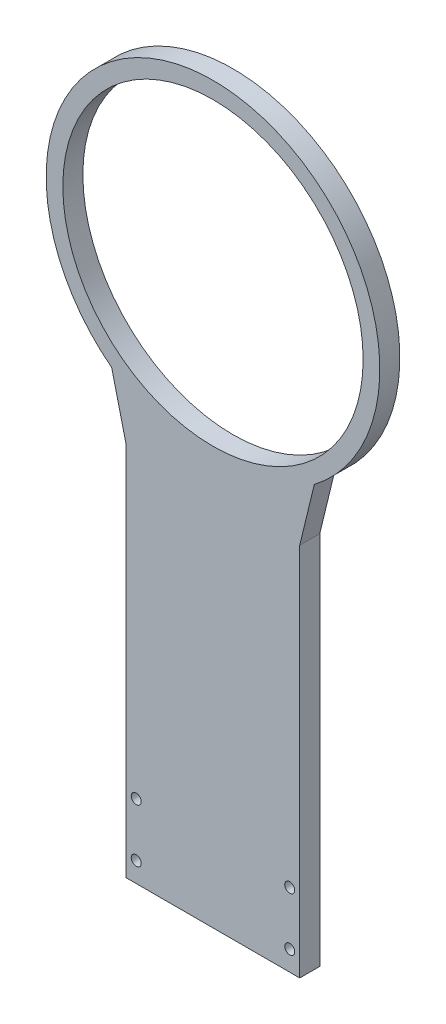
SolidWorks part; units mm, degrees
ref_plane "Front" through (0, 0, 0) normal (0, 0, 1) x (1, 0, 0)
ref_plane "Top" through (0, 0, 0) normal (0, 1, 0) x (1, 0, 0)
ref_plane "Right" through (0, 0, 0) normal (1, 0, 0) x (0, 0, -1)
sketch "Esquisse1" plane through (0, 0, 0) normal (0, 0, 1) x (1, 0, 0)
  line L1 (0, 0) -> (100, 0)
  line L2 (0, 0) -> (0, 100)
  line L3 (0, 100) -> (100, 100)
  line L4 (100, 0) -> (100, 100)
  dimension "D1" = 100
  dimension "D2" = 100
extrude "Boss.-Extru.1" add sketch "Esquisse1" along normal blind 6
sketch "Esquisse2" plane through (0, 0, 6) normal (0, 0, 1) x (1, 0, 0)
  line L1 (50, 0) -> (50, 100) construction
  line L2 (0, 0) -> (100, 0) construction
  line L3 (100, 100) -> (0, 100) construction
  circle A0 centre (50, 50) radius 45
  dimension "D1" = 90
extrude "Enlèv. mat.-Extru.1" cut sketch "Esquisse2" against normal through all
sketch "Esquisse3" plane through (0, 0, 6) normal (0, 0, 1) x (1, 0, 0)
  line L0 (100, 0) -> (100, 100) construction
  line L1 (0, 0) -> (100, 0)
  line L2 (0, 0) -> (0, -120)
  line L3 (0, -120) -> (100, -120)
  line L4 (100, 0) -> (100, -120)
  dimension "D1" = 120
extrude "Boss.-Extru.2" add sketch "Esquisse3" against normal up to vertex (6 mm away) up to point (100, 0, 0)
sketch "Esquisse4" plane through (0, 0, 6) normal (0, 0, 1) x (1, 0, 0)
  line L0 (50, -120) -> (50, -3.3563) construction
  line L1 (0, -120) -> (100, -120) construction
  line L2 (0, 100) -> (0, -120) construction
  line L3 (24, -120) -> (0, -120)
  line L4 (24, -120) -> (24, 0)
  line L5 (24, 0) -> (0, 0)
  line L6 (0, -120) -> (0, 0)
  line L7 (100, -120) -> (100, 0)
  line L8 (76, 0) -> (100, 0)
  line L9 (76, -120) -> (76, 0)
  line L10 (76, -120) -> (100, -120)
  dimension "D1" = 52
  dimension "D2" = 120
extrude "Enlèv. mat.-Extru.2" cut sketch "Esquisse4" against normal up to vertex (126 mm away) up to point (0, 100, -120)
sketch "Esquisse5" plane through (0, 0, 6) normal (0, 0, 1) x (1, 0, 0)
  line L0 (50, -120) -> (50, -10.2588) construction
  line L1 (24, -120) -> (76, -120) construction
  line L2 (27, -120) -> (27, -98) construction
  line L3 (24, -120) -> (24, 0) construction
  circle A0 centre (27, -98) radius 1.5
  circle A1 centre (27, -114) radius 1.5
  circle A2 centre (73, -114) radius 1.5
  circle A3 centre (73, -98) radius 1.5
  dimension "D1" = 16
  dimension "D2" = 6
  dimension "D4" = 3
  dimension "D3" = 3
extrude "Enlèv. mat.-Extru.3" cut sketch "Esquisse5" against normal through all
sketch "Esquisse6" plane through (0, 0, 6) normal (0, 0, 1) x (1, 0, 0)
  line L0 (76, 7.2917) -> (76, 0)
  line L1 (24, 0) -> (24, 7.2917)
  line L2 (100, 0) -> (100, 100) construction
  line L3 (24, 0) -> (-1, 0)
  line L4 (-1, 0) -> (-1, 101)
  line L5 (50, 50) -> (50, 80.2211) construction
  line L6 (50, 80.2211) -> (50, 101) construction
  line L7 (-1, 101) -> (101, 101)
  line L8 (100, 100) -> (0, 100) construction
  line L9 (0, 100) -> (0, 0) construction
  line L10 (76, 0) -> (101, 0)
  line L11 (101, 0) -> (101, 101)
  arc A0 (24, 7.2917) -> (76, 7.2917) centre (50, 50) cw
  dimension "D1" = 1
  dimension "D2" = 1
extrude "Enlèv. mat.-Extru.4" cut sketch "Esquisse6" against normal through all
chamfer "Chanfrein1" distance 5 angle 45 2 edges at (24, 7.2917, 3) (76, 7.2917, 3) first distance on face at (50, 53.6458, 3)
